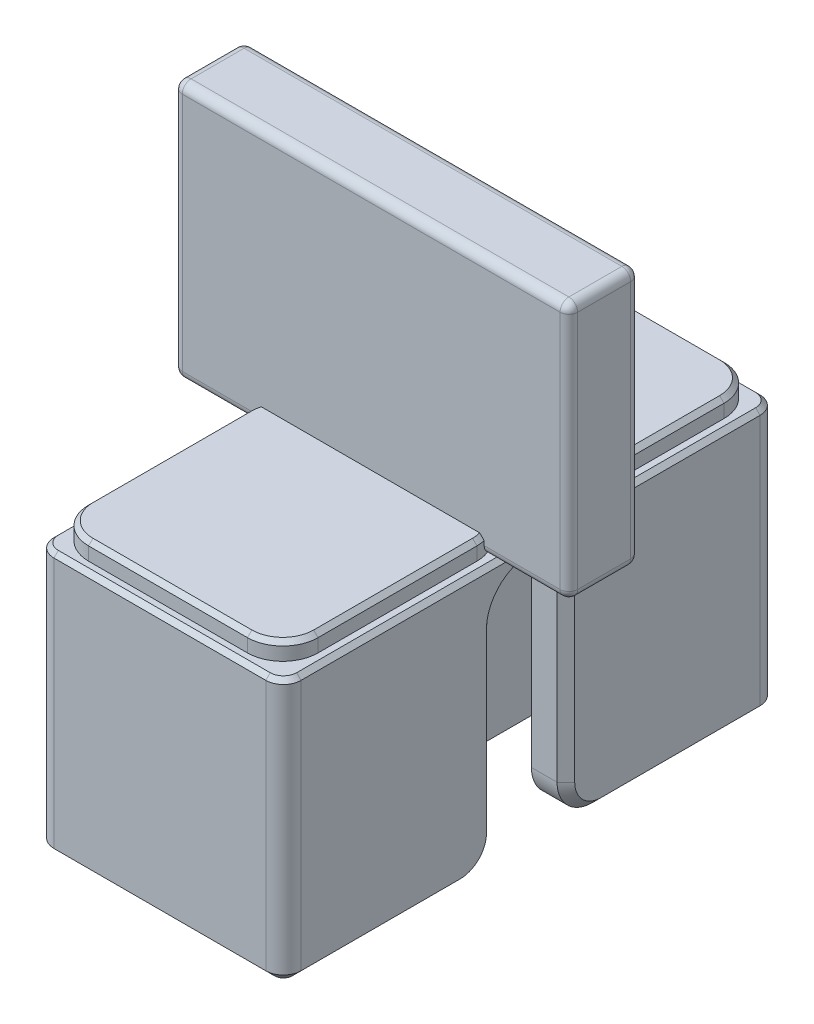
SolidWorks part; units mm, degrees
other "Case"
ref_plane "Front Plane" through (0, 0, 0) normal (0, 0, 1) x (1, 0, 0)
ref_plane "Top Plane" through (0, 0, 0) normal (0, 1, 0) x (1, 0, 0)
ref_plane "Right Plane" through (0, 0, 0) normal (1, 0, 0) x (0, 0, -1)
sketch "Sketch1" plane through (0, 0, 0) normal (0, 1, 0) x (1, 0, 0)
  line L1 (-56, -10) -> (56, -10)
  line L2 (-56, -10) -> (-56, 10)
  line L3 (-56, 10) -> (56, 10)
  line L4 (56, -10) -> (56, 10)
  line L5 (-56, -10) -> (56, 10) construction
  line L6 (-56, 10) -> (56, -10) construction
  point P0 (0, 0)
extrude "Boss-Extrude1" add sketch "Sketch1" along normal blind 73
fillet "Fillet1" radius 2.5 12 edges at (56, 0, 0) (0, 0, -10) (-56, 0, 0) (0, 0, 10) (56, 73, 0) (-56, 36.5, -10) (56, 36.5, -10) (56, 36.5, 10) (-56, 36.5, 10) (0, 73, 10) (0, 73, -10) (-56, 73, 0)
sketch "Sketch7" plane through (0, 0, 0) normal (0, 1, 0) x (1, 0, 0)
  line L0 (-22.7027, 2.6621) -> (22.2973, 2.6621)
  line L1 (32.2973, 12.6621) -> (32.2973, 57.6621)
  line L2 (22.2973, 67.6621) -> (-22.7027, 67.6621)
  line L3 (-32.7027, 57.6621) -> (-32.7027, 12.6621)
  line L4 (-35.2027, 70.1621) -> (34.7973, 70.1621)
  line L5 (-35.2027, 70.1621) -> (-35.2027, -69.8379)
  line L6 (-35.2027, -69.8379) -> (34.7973, -69.8379)
  line L7 (32.2973, -57.3379) -> (32.2973, -12.3379)
  line L8 (-22.7027, -67.3379) -> (22.2973, -67.3379)
  line L9 (-32.7027, -12.3379) -> (-32.7027, -57.3379)
  line L10 (22.2973, -2.3379) -> (-22.7027, -2.3379)
  line L11 (34.7973, 70.1621) -> (34.7973, -69.8379)
  arc A0 (22.2973, 2.6621) -> (32.2973, 12.6621) centre (22.2973, 12.6621) ccw
  arc A1 (32.2973, 57.6621) -> (22.2973, 67.6621) centre (22.2973, 57.6621) ccw
  arc A2 (-22.7027, 67.6621) -> (-32.7027, 57.6621) centre (-22.7027, 57.6621) ccw
  arc A3 (-32.7027, 12.6621) -> (-22.7027, 2.6621) centre (-22.7027, 12.6621) ccw
  arc A4 (22.2973, -67.3379) -> (32.2973, -57.3379) centre (22.2973, -57.3379) ccw
  arc A5 (-32.7027, -57.3379) -> (-22.7027, -67.3379) centre (-22.7027, -57.3379) ccw
  arc A6 (-22.7027, -2.3379) -> (-32.7027, -12.3379) centre (-22.7027, -12.3379) ccw
  arc A7 (32.2973, -12.3379) -> (22.2973, -2.3379) centre (22.2973, -12.3379) ccw
extrude "Boss-Extrude5" add sketch "Sketch7" along normal blind 5 separate body contours L7 A7 L10 A6 L9 A5 L8 A4 | L3 A3 L0 A0 L1 A1 L2 A2 region at (-0.2027, 0, -35.1621) region at (-0.2027, 0, 34.8379)
sketch "Sketch9" plane through (0, 0, 0) normal (0, -1, 0) x (1, 0, 0)
  line L4 (-29.6336, 70.2172) -> (30.3664, 70.2172)
  line L5 (-34.6336, 65.2172) -> (-34.6336, -64.7828)
  line L6 (-29.6336, -69.7828) -> (30.3664, -69.7828)
  line L11 (35.3664, 65.2172) -> (35.3664, -64.7828)
  arc A8 (-34.6336, -64.7828) -> (-29.6336, -69.7828) centre (-29.6336, -64.7828) ccw
  arc A9 (30.3664, -69.7828) -> (35.3664, -64.7828) centre (30.3664, -64.7828) ccw
  arc A10 (30.3664, 70.2172) -> (35.3664, 65.2172) centre (30.3664, 65.2172) cw
  arc A11 (-29.6336, 70.2172) -> (-34.6336, 65.2172) centre (-29.6336, 65.2172) ccw
  dimension "D1" = 5
extrude "Boss-Extrude9" add sketch "Sketch9" along normal blind 5
sketch "Sketch10" plane through (0, -5, 0) normal (0, -1, 0) x (1, 0, 0)
  line L0 (0, 0) -> (-52.5498, 0) construction
  line L1 (0, 0) -> (0, 23.1673) construction
  line L2 (0.3664, 70.2172) -> (2.8664, 70.2172)
  line L5 (-29.6336, 70.2172) -> (30.3664, 70.2172)
  line L6 (-34.6336, 65.2172) -> (-34.6336, -64.7828)
  line L7 (-29.6336, -69.7828) -> (30.3664, -69.7828)
  line L8 (35.3664, 65.2172) -> (35.3664, -64.7828)
  line L11 (-2.8664, 55.5) -> (-25.3664, 55.5)
  line L12 (-25.3664, -55.5) -> (-25.3664, 55.5)
  line L13 (-2.8664, -55.5) -> (-25.3664, -55.5)
  line L14 (-2.8664, 55.5) -> (-2.8664, -55.5)
  line L15 (2.8664, 55.5) -> (2.8664, -55.5)
  line L16 (2.8664, 55.5) -> (25.3664, 55.5)
  line L17 (2.8664, -55.5) -> (25.3664, -55.5)
  line L18 (25.3664, -55.5) -> (25.3664, 55.5)
  arc A0 (30.3664, -69.7828) -> (35.3664, -64.7828) centre (30.3664, -64.7828) ccw
  arc A1 (30.3664, 70.2172) -> (35.3664, 65.2172) centre (30.3664, 65.2172) cw
  arc A2 (-29.6336, 70.2172) -> (-34.6336, 65.2172) centre (-29.6336, 65.2172) ccw
  arc A3 (-34.6336, -64.7828) -> (-29.6336, -69.7828) centre (-29.6336, -64.7828) ccw
  point P6 (0, 0)
  arc M27 (-34.6336, -64.7828) -> (-29.6336, -69.7828) centre (-29.6336, -64.7828) ccw
  line M28 (-29.6336, -69.7828) -> (30.3664, -69.7828)
  arc M29 (30.3664, -69.7828) -> (35.3664, -64.7828) centre (30.3664, -64.7828) ccw
  line M30 (35.3664, -64.7828) -> (35.3664, 65.2172)
  arc M31 (35.3664, 65.2172) -> (30.3664, 70.2172) centre (30.3664, 65.2172) ccw
  line M32 (30.3664, 70.2172) -> (-29.6336, 70.2172)
  arc M33 (-29.6336, 70.2172) -> (-34.6336, 65.2172) centre (-29.6336, 65.2172) ccw
  line M34 (-34.6336, 65.2172) -> (-34.6336, -64.7828)
  dimension "D1" = 5
  dimension "D2" = 5
extrude "Boss-Extrude10" add sketch "Sketch10" along normal blind 70 contours L18 L17 L15 L16 L11 L14 L13 L12 M34 M27 M28 M29 M30 M31 M32 M33 region at (0.749, -5, 0.4441)
sketch "Sketch11" plane through (-34.6336, 0, 0) normal (-1, 0, 0) x (0, 0, 1)
  line L0 (0.2172, -5) -> (-9.7828, -5)
  line L2 (65.2172, -75) -> (-64.7828, -75) construction
  line L3 (10.2172, -75) -> (-9.7828, -75)
  line L4 (-9.7828, -75) -> (-9.7828, -5)
  line L7 (10.2172, -75) -> (10.2172, -5)
  line L8 (10.2172, -5) -> (0.2172, -5)
extrude "Cut-Extrude1" cut sketch "Sketch11" against normal blind 70
fillet "Fillet14" radius 10 6 edges at (-30, -5, 10.2172) (-30, -5, -9.7828) (0, -5, -9.7828) (0, -5, 10.2172) (30.3664, -5, 10.2172) (30.3664, -5, -9.7828)
fillet "Fillet15" radius 10 6 edges at (30.3664, -75, 10.2172) (0, -75, 10.2172) (-30, -75, 10.2172) (-30, -75, -9.7828) (0, -75, -9.7828) (30.3664, -75, -9.7828)
chamfer "Chamfer1" distance 2.5 angle 45 22 edges at (-34.6336, -75, 42.7172) (-34.6336, -72.0711, 13.1462) (-33.1691, -75, 68.7528) (-34.6336, -40, 10.2172) (0.3664, -75, 70.2172) (-34.6336, -7.9289, 7.2883) (33.9019, -75, 68.7528) (-34.6336, -7.9289, -6.8538) (35.3664, -75, 42.7172) (-34.6336, -40, -9.7828) (35.3664, -72.0711, 13.1462) (-34.6336, -72.0711, -12.7117) (35.3664, -40, 10.2172) (-34.6336, -75, -42.2828) (35.3664, -7.9289, 7.2883) (-33.1691, -75, -68.3183) (35.3664, -7.9289, -6.8538) (0.3664, -75, -69.7828) (35.3664, -40, -9.7828) (33.9019, -75, -68.3183) (35.3664, -72.0711, -12.7117) (35.3664, -75, -42.2828)
chamfer "Chamfer2" distance 1.25 angle 45 16 edges at (-32.7027, 5, -35.1621) (-29.7737, 5, -5.5911) (-29.7737, 5, -64.7332) (-0.2027, 5, -2.6621) (-0.2027, 5, -67.6621) (29.3684, 5, -5.5911) (29.3684, 5, -64.7332) (32.2973, 5, -35.1621) (-32.7027, 5, 34.8379) (-29.7737, 5, 64.4089) (-29.7737, 5, 5.2668) (-0.2027, 5, 67.3379) (-0.2027, 5, 2.3379) (29.3684, 5, 64.4089) (29.3684, 5, 5.2668) (32.2973, 5, 34.8379)
sketch "Sketch12" plane through (0, -75, 0) normal (0, -1, 0) x (1, 0, 0)
  line L53 (-2.6164, -19.7828) -> (-2.6164, -9.7828)
  line L54 (-2.6164, -9.7828) -> (-2.6164, 0.2172)
  line L55 (-2.6164, 55.75) -> (-25.6164, 55.75)
  line L56 (-25.6164, 55.75) -> (-25.6164, 0.2172)
  line L57 (-2.6164, 0.2172) -> (-2.6164, 55.75)
  line L58 (-2.6164, -55.75) -> (-2.6164, -19.7828)
  line L59 (-25.6164, -55.75) -> (-2.6164, -55.75)
  line L60 (-25.6164, 0.2172) -> (-25.6164, -55.75)
  line L61 (-2.6164, -19.7828) -> (-2.6164, -9.7828)
  line L62 (-2.6164, -9.7828) -> (-2.6164, 0.2172)
  line L63 (-2.6164, 55.75) -> (-25.6164, 55.75)
  line L64 (-25.6164, 55.75) -> (-25.6164, 0.2172)
  line L65 (-2.6164, 0.2172) -> (-2.6164, 55.75)
  line L66 (-2.6164, -55.75) -> (-2.6164, -19.7828)
  line L67 (-25.6164, -55.75) -> (-2.6164, -55.75)
  line L68 (-25.6164, 0.2172) -> (-25.6164, -55.75)
  dimension "D1" = 0.25
extrude "Cut-Extrude2" cut sketch "Sketch12" against normal blind 70
sketch "Sketch13" plane through (0, -75, 0) normal (0, -1, 0) x (1, 0, 0)
  line L123 (2.6164, 55.5) -> (26.3079, 55.5)
  line L134 (25.6164, 0.2172) -> (25.6164, 10.2172)
  line L135 (25.6164, -9.7828) -> (25.6164, 0.2172)
  line L136 (25.6164, -19.7828) -> (25.6164, -9.7828)
  line L137 (25.6164, 20.2172) -> (25.6164, 55.5)
  line L138 (25.6164, 10.2172) -> (25.6164, 20.2172)
  line L139 (2.6164, 55.5) -> (2.6164, 0.2172)
  line L140 (2.6164, 0.2172) -> (2.6164, -9.7828)
  line L141 (2.6164, -9.7828) -> (2.6164, -19.7828)
  line L142 (2.6164, -19.7828) -> (2.6164, -55.75)
  line L143 (25.6164, -55.75) -> (25.6164, -19.7828)
  line L144 (2.6164, -55.75) -> (25.6164, -55.75)
  line L145 (25.6164, 0.2172) -> (25.6164, 10.2172)
  line L146 (25.6164, -9.7828) -> (25.6164, 0.2172)
  line L147 (25.6164, -19.7828) -> (25.6164, -9.7828)
  line L148 (25.6164, 20.2172) -> (25.6164, 55.5)
  line L149 (25.6164, 10.2172) -> (25.6164, 20.2172)
  line L150 (2.6164, 55.5) -> (2.6164, 0.2172)
  line L151 (2.6164, 0.2172) -> (2.6164, -9.7828)
  line L152 (2.6164, -9.7828) -> (2.6164, -19.7828)
  line L153 (2.6164, -19.7828) -> (2.6164, -55.75)
  line L154 (25.6164, -55.75) -> (25.6164, -19.7828)
  line L155 (2.6164, -55.75) -> (25.6164, -55.75)
  line M19 (32.8664, -19.7828) -> (25.3664, -19.7828)
  line M20 (25.3664, -19.7828) -> (25.3664, -55.5)
  line M21 (25.3664, -55.5) -> (2.8664, -55.5)
  line M22 (2.8664, -55.5) -> (2.8664, -19.7828)
  line M23 (2.8664, -19.7828) -> (-2.6164, -19.7828)
  dimension "D1" = 0.25
extrude "Cut-Extrude3" cut sketch "Sketch13" against normal blind 70 contours L151 L152 L147 L146 L145 L149 L148 L123 L150 M23 M22 M21 M20 M19 region at (14.1164, -75, 0.2652)
chamfer "Chamfer3" distance 1.25 angle 45 8 edges at (-33.1691, 0, 68.7528) (-34.6336, 0, 0.2172) (0.3664, 0, 70.2172) (-33.1691, 0, -68.3183) (33.9019, 0, 68.7528) (0.3664, 0, -69.7828) (35.3664, 0, 0.2172) (33.9019, 0, -68.3183)
